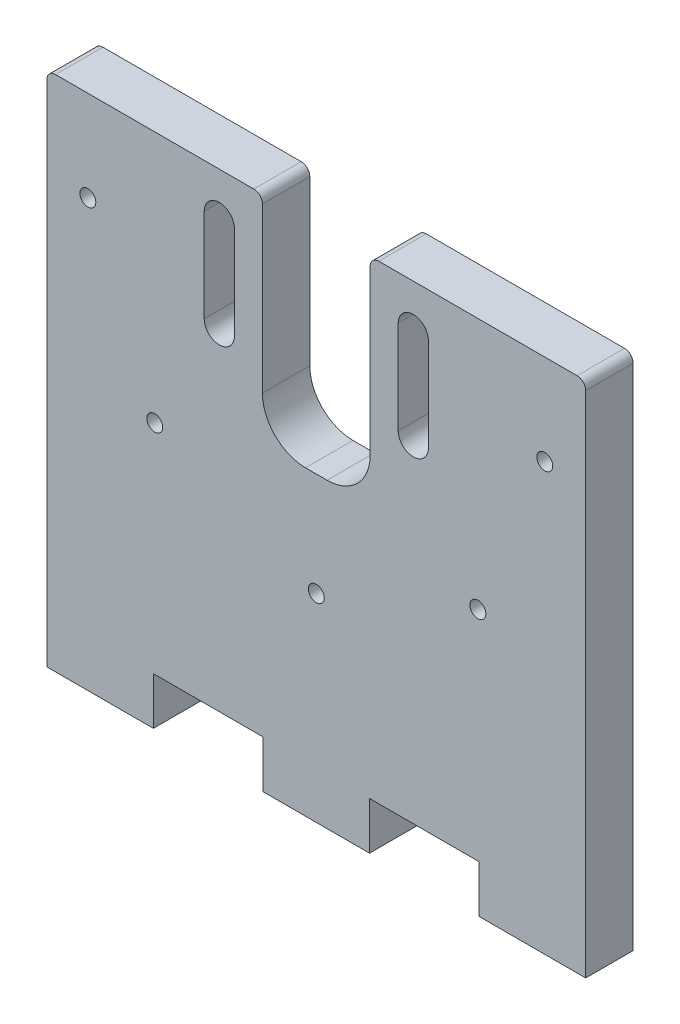
SolidWorks part; units mm, degrees
ref_plane "Front Plane" through (0, 0, 0) normal (0, 0, 1) x (1, 0, 0)
ref_plane "Top Plane" through (0, 0, 0) normal (0, 1, 0) x (1, 0, 0)
ref_plane "Right Plane" through (0, 0, 0) normal (1, 0, 0) x (0, 0, -1)
sketch "Sketch2" plane through (0, 0, 0) normal (0, 0, 1) x (1, 0, 0)
  line L1 (-0.1872, 0) -> (-0.1872, 118)
  line L9 (1.8128, 120) -> (47.8128, 120)
  line L10 (49.8128, 118) -> (49.8128, 80)
  line L11 (59.8128, 70) -> (64.8128, 70)
  line L12 (74.8128, 80) -> (74.8128, 118)
  line L13 (76.8128, 120) -> (122.8128, 120)
  line L14 (124.8128, 118) -> (124.8128, 0)
  line L16 (39.8128, 88.1904) -> (39.8128, 109.8096) construction
  line L17 (36.3128, 88.1904) -> (36.3128, 109.8096)
  line L18 (43.3128, 88.1904) -> (43.3128, 109.8096)
  line L19 (-0.1872, 0) -> (24.5128, 0)
  line L20 (84.8128, 88.1904) -> (84.8128, 109.8096) construction
  line L21 (88.3128, 88.1904) -> (88.3128, 109.8096)
  line L22 (81.3128, 88.1904) -> (81.3128, 109.8096)
  line L23 (24.5128, 0) -> (24.5128, 11)
  line L24 (24.5128, 11) -> (49.9628, 11)
  line L25 (49.9628, 11) -> (49.9628, 0)
  line L26 (49.9628, 0) -> (74.6628, 0)
  line L27 (74.6628, 0) -> (74.6628, 11)
  line L28 (74.6628, 11) -> (100.1128, 11)
  line L29 (100.1128, 11) -> (100.1128, 0)
  line L30 (100.1128, 0) -> (124.8128, 0)
  line L32 (49.8128, 70) -> (74.8128, 70) construction
  line L33 (49.8128, 70) -> (49.8128, 128) construction
  line L34 (49.8128, 128) -> (74.8128, 128) construction
  line L35 (74.8128, 70) -> (74.8128, 128) construction
  line L36 (49.8128, 70) -> (74.8128, 128) construction
  line L37 (49.8128, 128) -> (74.8128, 70) construction
  arc A6 (59.8128, 70) -> (49.8128, 80) centre (59.8128, 80) cw
  arc A7 (64.8128, 70) -> (74.8128, 80) centre (64.8128, 80) ccw
  arc A8 (49.8128, 118) -> (47.8128, 120) centre (47.8128, 118) ccw
  arc A9 (76.8128, 120) -> (74.8128, 118) centre (76.8128, 118) ccw
  arc A10 (1.8128, 120) -> (-0.1872, 118) centre (1.8128, 118) ccw
  arc A11 (124.8128, 118) -> (122.8128, 120) centre (122.8128, 118) ccw
  arc A14 (36.3128, 88.1904) -> (43.3128, 88.1904) centre (39.8128, 88.1904) ccw
  arc A15 (43.3128, 109.8096) -> (36.3128, 109.8096) centre (39.8128, 109.8096) ccw
  arc A16 (88.3128, 88.1904) -> (81.3128, 88.1904) centre (84.8128, 88.1904) cw
  arc A17 (81.3128, 109.8096) -> (88.3128, 109.8096) centre (84.8128, 109.8096) cw
  circle A23 centre (62.3128, 99) radius 53 construction
  circle A24 centre (62.3128, 46) radius 1.85
  circle A25 centre (24.8361, 61.5233) radius 1.85
  circle A26 centre (9.3128, 99) radius 1.85
  circle A27 centre (24.8361, 136.4767) radius 1.85 [skipped]
  circle A28 centre (62.3128, 152) radius 1.85 [skipped]
  circle A29 centre (99.7894, 136.4767) radius 1.85 [skipped]
  circle A30 centre (115.3128, 99) radius 1.85
  circle A31 centre (99.7894, 61.5233) radius 1.85
  point P23 (49.8128, 99)
  point P24 (39.8128, 99)
  point P32 (84.8128, 99)
  point P45 (62.3128, 99)
  point P50 (34.4855, 63.6613)
  point P51 (62.3128, 99)
  point P69 (62.3128, 99)
  dimension "D1" = 125
  dimension "D2" = 120
  dimension "D3" = 2
  dimension "D4" = 2
  dimension "D5" = 2
  dimension "D6" = 2
  dimension "D8" = 106
  dimension "D7" = 11
  dimension "D9" = 3.7
  dimension "D10" = 8
  dimension "D11" = 24.7
extrude "Boss-Extrude7" add sketch "Sketch2" along normal blind 11
